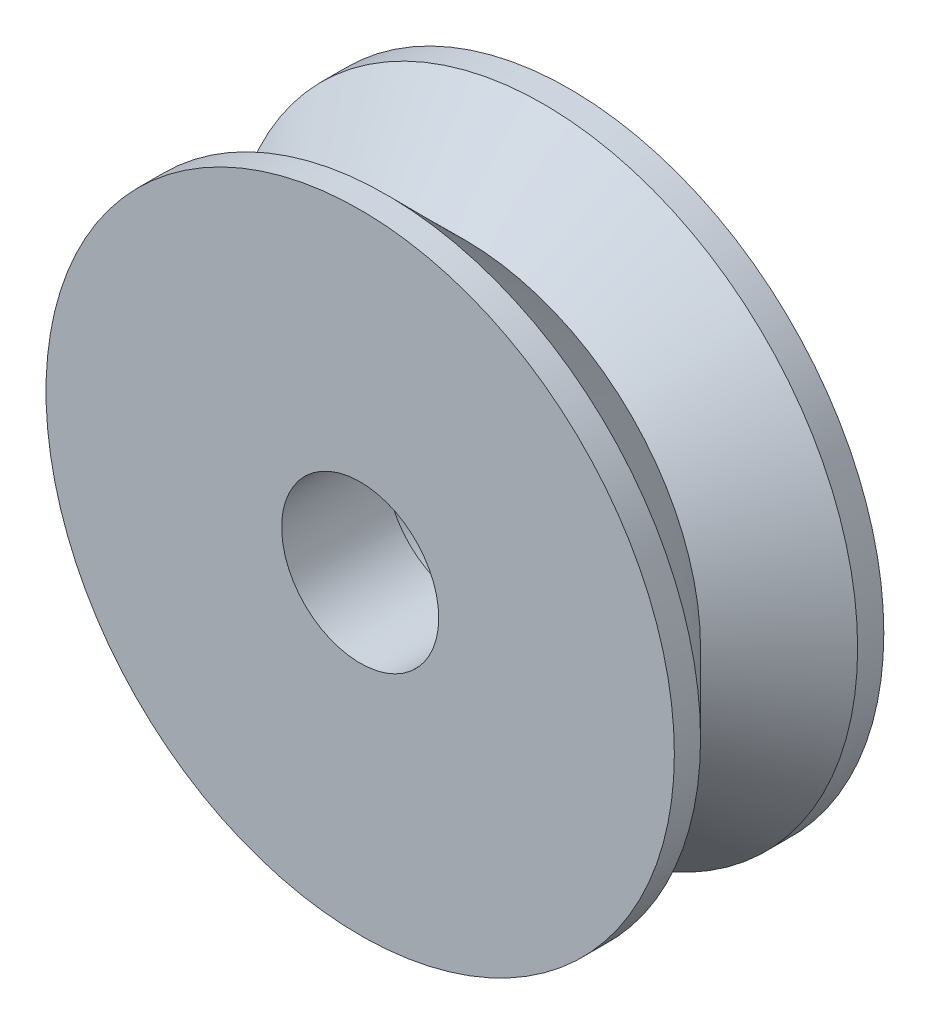
SolidWorks part; units mm, degrees
ref_plane "Front Plane" through (0, 0, 0) normal (0, 0, 1) x (1, 0, 0)
ref_plane "Top Plane" through (0, 0, 0) normal (0, 1, 0) x (1, 0, 0)
ref_plane "Right Plane" through (0, 0, 0) normal (1, 0, 0) x (0, 0, -1)
sketch "Sketch1" plane through (0, 0, 0) normal (0, 0, 1) x (1, 0, 0)
  circle A0 centre (0, 0) radius 6
  circle A1 centre (0, 0) radius 1.9
  dimension "D1" = 3.8
  dimension "D2" = 12
extrude "Boss-Extrude1" add sketch "Sketch1" along normal blind 2
chamfer "Chamfer1" distance 1.5 angle 45 1 edges at (6, 0, 2)
sketch "Sketch2" plane through (0, 0, 2) normal (0, 0, 1) x (1, 0, 0)
  circle A0 centre (0, 0) radius 6
  circle A1 centre (0, 0) radius 1.5
  circle A2 centre (0, 0) radius 4.5 construction
  dimension "D1" = 3
  dimension "D2" = 12
extrude "Boss-Extrude2" add sketch "Sketch2" along normal blind 2
chamfer "Chamfer2" distance 1.5 angle 45 1 edges at (6, 0, 2)
equation "\"D1@Sketch1\"= 3 + \"tol1@parametersSketch@prostheticParameters.SLDPRT\" * 2"
